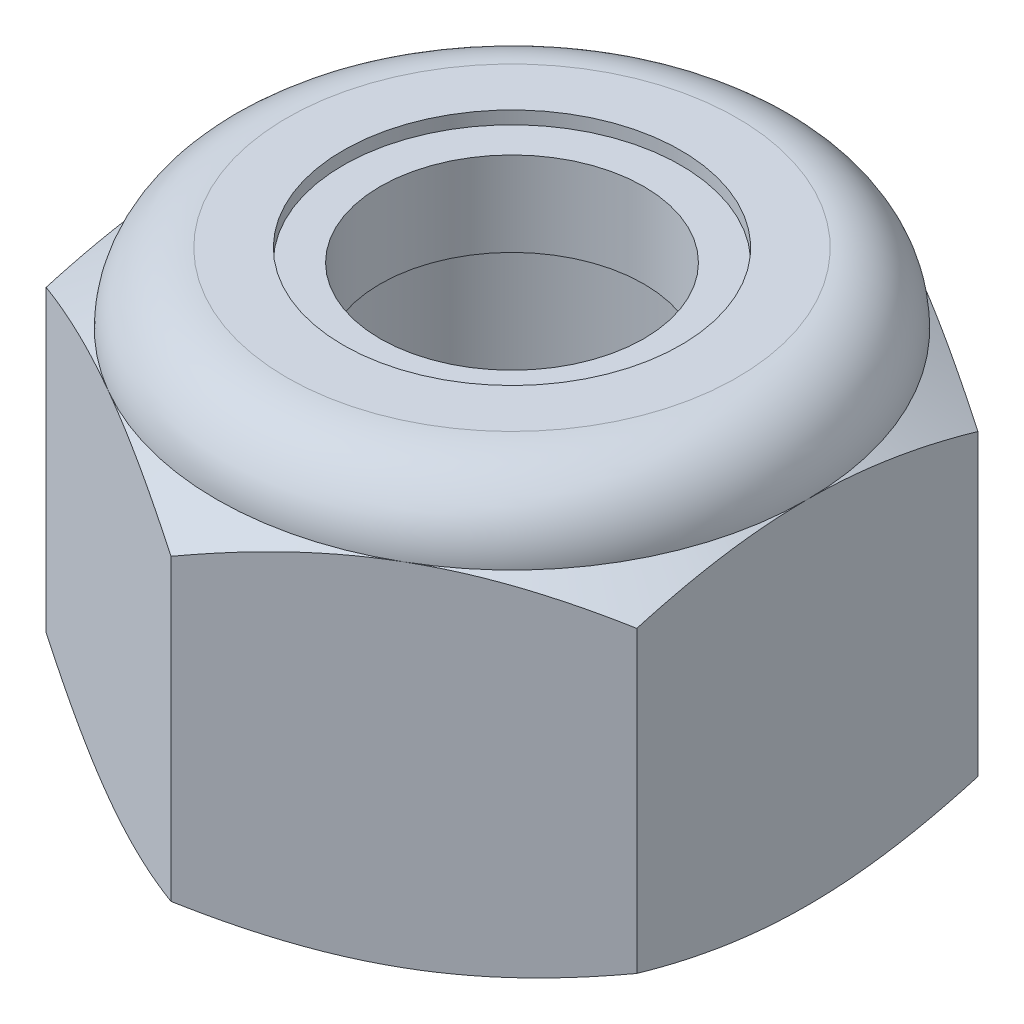
SolidWorks part; units mm, degrees
material "Stainless Steel (ferritic)"
ref_plane "Front" through (0, 0, 0) normal (0, 0, 1) x (1, 0, 0)
ref_plane "Top" through (0, 0, 0) normal (0, 1, 0) x (1, 0, 0)
ref_plane "Right" through (0, 0, 0) normal (1, 0, 0) x (0, 0, -1)
sketch "Sketch1" plane through (0, 0, 0) normal (0, 1, 0) x (1, 0, 0)
  line L1 (0, 4.0415) -> (-3.5, 2.0207)
  line L2 (-3.5, 2.0207) -> (-3.5, -2.0207)
  line L3 (-3.5, -2.0207) -> (0, -4.0415)
  line L4 (0, -4.0415) -> (3.5, -2.0207)
  line L5 (3.5, -2.0207) -> (3.5, 2.0207)
  line L6 (3.5, 2.0207) -> (0, 4.0415)
  circle A0 centre (0, 0) radius 3.5 construction
  dimension "Hex Flats" = 7
extrude "Extrude1" add sketch "Sketch1" along normal blind 5
sketch "Sketch13" plane through (0, 5, 0) normal (0, 1, 0) x (1, 0, 0)
  circle A0 centre (0, 0) radius 3.5 construction
  circle A1 centre (0, 0) radius 3.5
sketch "Sketch7" plane through (0, 0, 0) normal (0, 1, 0) x (1, 0, 0)
  circle A0 centre (0, 0) radius 2
  dimension "Thread OD" = 4
extrude "Cut-Extrude4" cut sketch "Sketch7" along normal through all
sketch "Sketch15" plane through (0, 0, 0) normal (0, 1, 0) x (1, 0, 0)
  circle A0 centre (0, 0) radius 2 construction
  circle A1 centre (0, 0) radius 2
curve "Helix/Spiral1" pitch 0.7 height 5.7 turns 8.1429 parameters "Pitch"=0.7
sketch "Sketch18" plane through (0, 0, 0) normal (1, 0, 0) x (0, 0, -1)
  line L0 (3.5, 1.8647) -> (3.5, 5) construction
  line L7 (3.5, 5) -> (3.5, 4.1667) construction
  line L8 (3.5, 5) -> (2.6667, 5) construction
  line L10 (3.5, 5) -> (-3.5, 5) construction
  line L11 (3.5, 4.1667) -> (4.0415, 4.1667)
  line L12 (4.0415, 5) -> (4.0415, 0) construction
  line L13 (4.0415, 4.1667) -> (4.0415, 5)
  line L14 (4.0415, 5) -> (2.6667, 5)
  arc A1 (3.5, 4.1667) -> (2.6667, 5) centre (2.6667, 4.1667) ccw
  dimension "D1" = 0.8333
revolve "Cut-Revolve1" cut sketch "Sketch18" angle 360 about axis through (0, 5, 0) along (0, -1, 0)
extrude "Cut-Extrude5" cut sketch "Sketch13" against normal through all draft 60 from surface flip side to cut starting at face at (0, 4.1667, -3.5242)
sketch "Sketch19" plane through (0, 0, 0) normal (0, -1, 0) x (1, 0, 0)
  circle A0 centre (0, 0) radius 3.5 construction
  circle A1 centre (0, 0) radius 3.5
extrude "Cut-Extrude6" cut sketch "Sketch19" against normal through all draft 60 flip side to cut
sketch "Sketch20" plane through (0, 5, 0) normal (0, 1, 0) x (1, 0, 0)
  circle A1 centre (0, 0) radius 2 construction
  circle A2 centre (0, 0) radius 1.5625
  circle A3 centre (0, 0) radius 1.5625
  circle A4 centre (0, 0) radius 2
  dimension "D1" = 0.4375
extrude "Boss-Extrude1" add sketch "Sketch20" against normal blind 1 from offset 0.1524 separate body offset against normal yes
sketch "Sketch24" plane through (0, 5, 0) normal (0, 1, 0) x (1, 0, 0)
  line L0 (0, 0) -> (0, -4.0415) construction
  line L2 (0, 0) -> (-1.4142, -1.4142) construction
  circle A0 centre (0, 0) radius 2 construction
  dimension "D1" = 45
sketch "Sketch21" plane through (0, 0, 0) normal (1, 0, 0) x (0, 0, -1)
  line L0 (2.0758, 0.0438) -> (2.0758, -0.6562) construction
  line L1 (2.0758, 0.0438) -> (1.4696, -0.3062) construction
  line L2 (1.4696, -0.3062) -> (2.0758, -0.6562) construction
  line L3 (2.0758, -0.3062) -> (2, -0.3062) construction
  line L4 (1.4696, -0.3062) -> (1.5453, -0.3062) construction
  line L5 (1.5453, -0.2625) -> (1.5453, -0.35) construction
  line L6 (2, 0) -> (2, -0.6125) construction
  line L7 (2.0379, 0.0219) -> (2.0379, -0.6344) construction
  line L8 (1.5453, -0.2625) -> (2, 0)
  line L9 (2, 0) -> (2, -0.6125)
  line L10 (2, -0.6125) -> (1.5453, -0.35)
  line L11 (1.5453, -0.35) -> (1.5453, -0.2625)
  line L15 (0, 0) -> (3.0311, 0) construction
  line L16 (2, 0) -> (2, 5) construction
  point P12 (2.0379, -0.3062)
  dimension "D1" = 0.7
  dimension "D2" = 0.0875
sweep "Sweep1" [suppressed] add profiles "Sketch21" path "Helix/Spiral1"
sketch "Sketch22" plane through (0, 0, 0) normal (0, -1, 0) x (1, 0, 0)
  circle A0 centre (0, 0) radius 2 construction
  circle A1 centre (0, 0) radius 2
extrude "Cut-Extrude7" [suppressed] cut sketch "Sketch22" against normal through all draft 45 and the other way through all
sketch "Sketch23" plane through (0, 5, 0) normal (0, 1, 0) x (1, 0, 0)
  circle A0 centre (0, 0) radius 2 construction
  circle A1 centre (0, 0) radius 2
extrude "Cut-Extrude8" [suppressed] cut sketch "Sketch23" along normal through all and the other way through all draft 45 from offset 1
ref_plane "Contact Plane 1" through (0, 5, 0) normal (0, 1, 0) x (1, 0, 0)
ref_plane "Contact Plane 2" through (0, 0, 0) normal (0, -1, 0) x (-1, 0, 0)
ref_axis "Center Axis 1" through (0, -4.1586, 0) along (0, 1, 0)
equation "\"D3@Helix/Spiral1\"=\"Height@Extrude1\"+\"Pitch@Helix/Spiral1\""
equation "\"D1@Sketch18\"=\"Height@Extrude1\"/6"
equation "\"D1@Sketch20\"=\"Pitch@Helix/Spiral1\"*.625"
equation "\"D2@Sketch21\"=\"Pitch@Helix/Spiral1\"/8"
equation "\"D1@Sketch21\"=\"Pitch@Helix/Spiral1\""
